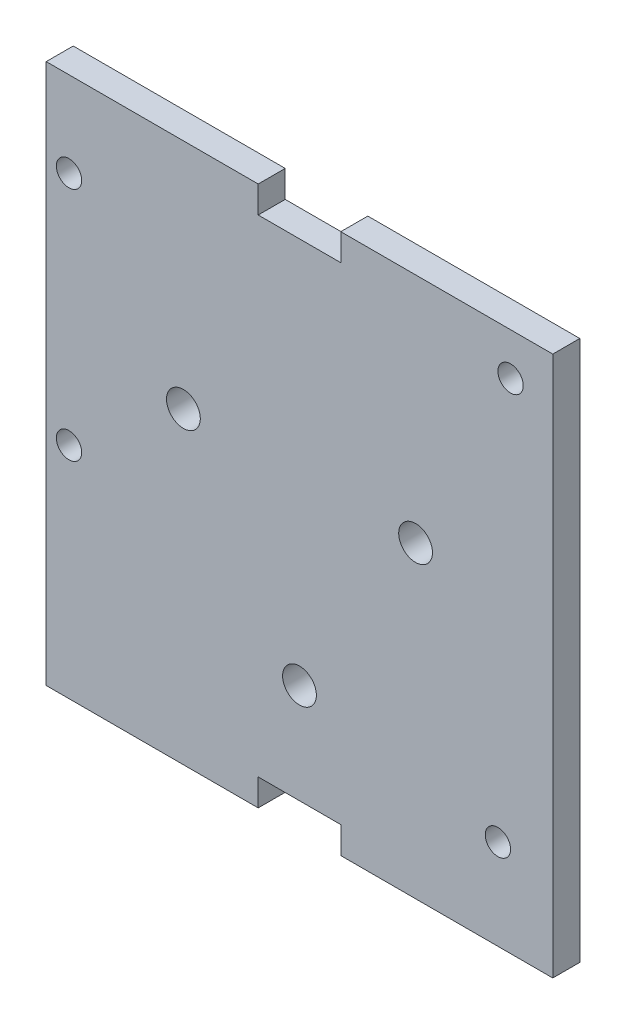
SolidWorks part; units mm, degrees
ref_plane "Front Plane" through (0, 0, 0) normal (0, 0, 1) x (1, 0, 0)
ref_plane "Top Plane" through (0, 0, 0) normal (0, 1, 0) x (1, 0, 0)
ref_plane "Right Plane" through (0, 0, 0) normal (1, 0, 0) x (0, 0, -1)
sketch "Sketch2" plane through (0, 0, 0) normal (0, 0, 1) x (1, 0, 0)
  line L1 (-32.5494, -8.3608) -> (27.4506, -8.3608)
  line L2 (-32.5494, -8.3608) -> (-32.5494, 55.6392)
  line L3 (-32.5494, 55.6392) -> (27.4506, 55.6392)
  line L4 (27.4506, -8.3608) -> (27.4506, 55.6392)
  dimension "D1" = 64
  dimension "D2" = 60
extrude "Top" add sketch "Sketch2" along normal blind 3.2
sketch "Sketch3" plane through (0, 0, 3.2) normal (0, 0, 1) x (1, 0, 0)
  line L0 (22.4506, 50.6392) -> (22.4506, 1.9043) construction
  line L4 (27.4506, 55.6392) -> (-32.5494, 55.6392) construction
  line L6 (27.4506, -8.3608) -> (27.4506, 55.6392) construction
  circle A0 centre (20.9506, 2.3392) radius 1.5
  circle A1 centre (22.4506, 50.6392) radius 1.5
  circle A2 centre (-29.8494, 17.6392) radius 1.5
  circle A3 centre (-29.8494, 45.5392) radius 1.5
  dimension "D1" = 3
  dimension "D2" = 48.3
  dimension "D7" = 5
  dimension "D3" = 27.9
  dimension "D4" = 5.1
  dimension "D5" = 50.8
  dimension "D6" = 5
extrude "Arduino Holes" cut sketch "Sketch3" against normal blind 3.2
sketch "Sketch5" plane through (0, 0, 0) normal (0, 0, -1) x (-1, 0, 0)
  line L0 (2.5494, -8.3608) -> (2.5494, 55.6392) construction
  line L1 (32.5494, -8.3608) -> (-27.4506, -8.3608) construction
  line L2 (-27.4506, 55.6392) -> (32.5494, 55.6392) construction
  circle A0 centre (2.5494, 6.6392) radius 2
  circle A1 centre (-11.2006, 28.1392) radius 2
  circle A2 centre (16.2994, 28.1392) radius 2
  dimension "D1" = 4
  dimension "D2" = 27.5
  dimension "D3" = 21.5
  dimension "D4" = 15
extrude "Battery Cut" cut sketch "Sketch5" against normal blind 3.2
sketch "Sketch7" plane through (0, 0, 0) normal (0, 0, -1) x (-1, 0, 0)
  line L0 (2.5494, -8.3608) -> (2.5494, 55.6392) construction
  line L1 (32.5494, -8.3608) -> (-27.4506, -8.3608) construction
  line L2 (-27.4506, 55.6392) -> (32.5494, 55.6392) construction
  line L4 (7.4394, 55.6392) -> (-2.3406, 55.6392)
  line L5 (7.4394, 55.6392) -> (7.4394, 52.4592)
  line L6 (7.4394, 52.4592) -> (-2.3406, 52.4592)
  line L7 (-2.3406, 55.6392) -> (-2.3406, 52.4592)
  line L8 (-2.3406, -8.3608) -> (7.4394, -8.3608)
  line L9 (-2.3406, -8.3608) -> (-2.3406, -5.1808)
  line L10 (-2.3406, -5.1808) -> (7.4394, -5.1808)
  line L11 (7.4394, -8.3608) -> (7.4394, -5.1808)
  dimension "D1" = 3.18
  dimension "D2" = 9.78
  dimension "D3" = 3.18
  dimension "D4" = 9.78
extrude "Friction Fit" cut sketch "Sketch7" against normal blind 10
sketch "Sketch4" [suppressed] plane through (0, 0, 0) normal (0, 0, 1) x (1, 0, 0)
  line L0 (0, 13.2972) -> (0, -11.8071) construction
  line L1 (30, -15) -> (-30, -15)
  line L2 (30, -15) -> (30, 15)
  line L3 (30, 15) -> (-30, 15)
  line L4 (-30, -15) -> (-30, 15)
  line L5 (17.7111, 0) -> (-18.0699, 0) construction
  dimension "D1" = 60
  dimension "D2" = 30
extrude "Side" [suppressed] add sketch "Sketch4" along normal blind 3.2
sketch "Sketch8" [suppressed] plane through (0, 15, 0) normal (0, 1, 0) x (1, 0, 0)
  line L0 (30, 0) -> (-30, 0) construction
  line L1 (5.11, 0) -> (-5.11, 0)
  line L2 (5.11, 0) -> (5.11, -3.2)
  line L3 (5.11, -3.2) -> (-5.11, -3.2)
  line L4 (-5.11, 0) -> (-5.11, -3.2)
  line L5 (30, -3.2) -> (-30, -3.2) construction
  line L6 (0, 0) -> (0, -3.2) construction
  dimension "D1" = 10.22
extrude "Friction Extrude" [suppressed] add sketch "Sketch8" along normal blind 3.18
mirror "Mirror" [suppressed] about plane through (0, 0, 0) normal (0, 1, 0)
equation "\"Kerf\"= .22"
